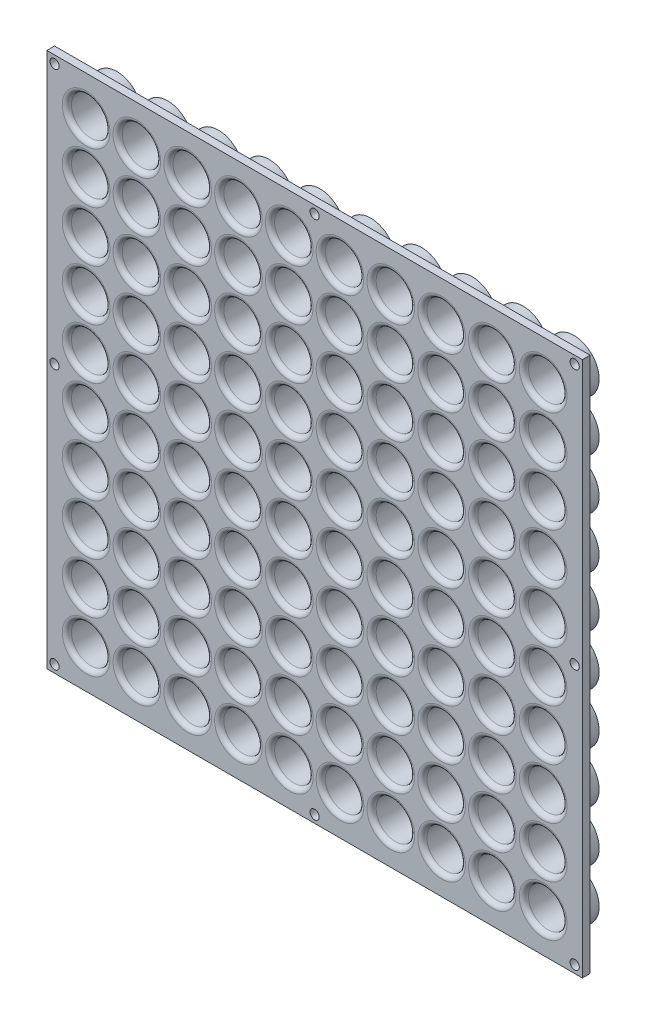
SolidWorks part; units mm, degrees
ref_plane "Ebene vorne" through (0, 0, 0) normal (0, 0, 1) x (1, 0, 0)
ref_plane "Ebene oben" through (0, 0, 0) normal (0, 1, 0) x (1, 0, 0)
ref_plane "Ebene rechts" through (0, 0, 0) normal (1, 0, 0) x (0, 0, -1)
sketch "Sketch1" plane through (0, 0, 0) normal (0, 0, 1) x (1, 0, 0)
  line L1 (0, 0) -> (-250, 0)
  line L2 (0, 0) -> (0, 250)
  line L3 (0, 250) -> (-250, 250)
  line L4 (-250, 0) -> (-250, 250)
  dimension "D1" = 250
  dimension "D2" = 250
extrude "Boss-Extrude1" add sketch "Sketch1" along normal blind 50
sketch "Sketch2" plane through (0, 0, 50) normal (0, 0, 1) x (1, 0, 0)
  line L0 (-125, 250) -> (-125, 0) construction
  line L1 (0, 250) -> (-250, 250) construction
  line L2 (-250, 0) -> (0, 0) construction
  line L5 (0, 0) -> (0, 250) construction
  line L7 (-55, 220) -> (-15, 220)
  line L8 (-55, 220) -> (-55, 120)
  line L9 (-55, 120) -> (-15, 120)
  line L10 (-15, 220) -> (-15, 120)
  line L14 (-55, 95) -> (-15, 95)
  line L15 (-55, 95) -> (-55, 45)
  line L16 (-55, 45) -> (-15, 45)
  line L17 (-15, 95) -> (-15, 45)
  dimension "D1" = 100
  dimension "D2" = 40
  dimension "D3" = 30
  dimension "D4" = 15
  dimension "D5" = 50
  dimension "D6" = 25
extrude "Cut-Extrude1" cut sketch "Sketch2" against normal blind 45
fillet "Fillet1" radius 5 4 edges at (-35, 120, 50) (-15, 170, 50) (-55, 170, 50) (-35, 220, 50)
fillet "Fillet2" radius 5 4 edges at (-35, 45, 50) (-15, 70, 50) (-35, 95, 50) (-55, 70, 50)
sketch "Sketch4" plane through (0, 0, 50) normal (0, 0, 1) x (1, 0, 0)
  line L0 (0, 250) -> (-250, 250) construction
  line L1 (-200, 250) -> (-175, 250)
  line L2 (-200, 250) -> (-200, 232.5)
  line L3 (-200, 232.5) -> (-175, 232.5)
  line L4 (-175, 250) -> (-175, 232.5)
  line L5 (-125, 250) -> (-125, 0) construction
  line L10 (-250, 0) -> (0, 0) construction
  line L11 (-50, 232.5) -> (-75, 232.5)
  line L12 (-75, 250) -> (-75, 232.5)
  line L13 (-50, 250) -> (-75, 250)
  line L14 (-50, 250) -> (-50, 232.5)
  dimension "D1" = 50
  dimension "D2" = 25
  dimension "D3" = 17.5
sketch "Sketch5" plane through (0, 0, 50) normal (0, 0, 1) x (1, 0, 0)
  line L0 (-235, 200) -> (-75, 200) construction
  line L1 (0, 250) -> (-250, 250) construction
  line L2 (-75, 200) -> (-75, 10) construction
  line L3 (-75, 10) -> (-235, 10) construction
  line L4 (-235, 10) -> (-235, 200) construction
  line L5 (-250, 250) -> (-250, 0) construction
  line L6 (-60, 115) -> (-60, 225) construction
  line L7 (-250, 0) -> (0, 0) construction
  line L9 (-235, 200) -> (-215, 200) construction
  line L10 (-235, 200) -> (-235, 180) construction
  line L11 (-235, 180) -> (-215, 180) construction
  line L12 (-215, 200) -> (-215, 180) construction
  line L13 (-235, 200) -> (-215, 180) construction
  line L14 (-235, 180) -> (-215, 200) construction
  circle A0 centre (-225, 190) radius 6.25
  dimension "D5" = 12.5
  dimension "D1" = 15
  dimension "D2" = 50
  dimension "D3" = 15
  dimension "D4" = 10
  dimension "D6" = 20
  dimension "D7" = 20
extrude "Cut-Extrude2" cut sketch "Sketch5" against normal blind 22
fillet "Fillet5" radius 1.5 1 edges at (-218.75, 190, 50)
pattern_linear "LPattern4" count 10 spacing 16.5 along (1, 0, 0) count 10 spacing 16.5 along (0, -1, 0) of "Cut-Extrude2", "Fillet5"
sketch "Sketch7" plane through (0, 0, 0) normal (0, 0, -1) x (-1, 0, 0)
  line L0 (250, 250) -> (250, 0) construction
  line L1 (5, 245) -> (245, 245)
  line L2 (5, 245) -> (5, 225)
  line L3 (5, 5) -> (245, 5)
  line L4 (245, 245) -> (245, 5)
  line L5 (0, 250) -> (250, 250) construction
  line L6 (0, 0) -> (0, 250) construction
  line L7 (250, 0) -> (0, 0) construction
  line L8 (5, 115) -> (5, 100)
  line L9 (5, 225) -> (60, 225)
  line L11 (5, 115) -> (60, 115)
  line L12 (60, 225) -> (60, 115)
  line L13 (5, 40) -> (60, 40)
  line L15 (5, 100) -> (60, 100)
  line L16 (60, 40) -> (60, 100)
  line L17 (5, 40) -> (5, 5)
  line L18 (60, 225) -> (10, 225) construction
  dimension "D1" = 5
  dimension "D2" = 5
  dimension "D3" = 5
  dimension "D4" = 5
extrude "Cut-Extrude4" cut sketch "Sketch7" against normal blind 45
sketch "Sketch8" plane through (0, 0, 50) normal (0, 0, 1) x (1, 0, 0)
  line L0 (0, 250) -> (-250, 250) construction
  line L1 (-175, 250) -> (-75, 250)
  line L2 (-175, 250) -> (-175, 230)
  line L3 (-175, 230) -> (-75, 230)
  line L4 (-75, 250) -> (-75, 230)
  point P6 (-125, 250)
  point P7 (-125, 250)
  dimension "D1" = 100
  dimension "D2" = 20
extrude "Cut-Extrude5" cut sketch "Sketch8" against normal blind 30
fillet "Fillet6" radius 2.5 2 edges at (-125, 230, 45) (-125, 230, 50)
fillet "Fillet7" radius 2 2 edges at (-125, 250, 20) (-125, 245, 20)
sketch "Sketch10" plane through (0, 0, 50) normal (0, 0, 1) x (1, 0, 0)
  line L2 (-35, 40) -> (-35, 0) construction
  line L3 (-10, 40) -> (-60, 40) construction
  line L4 (-250, 0) -> (0, 0) construction
  circle A0 centre (-35, 20) radius 13.5
  dimension "D1" = 27
extrude "Cut-Extrude6" cut sketch "Sketch10" against normal through all
extrude "Cut-Extrude7" cut sketch "Sketch4" against normal blind 10
sketch "Sketch12" plane through (0, 0, 45) normal (0, 0, -1) x (-1, 0, 0)
  line L0 (17.3, 19.25) -> (51.5, 19.25) construction
  line L1 (17.3, 32.5) -> (51.5, 32.5) construction
  line L2 (17.3, 32.5) -> (17.3, 6) construction
  line L3 (17.3, 6) -> (51.5, 6) construction
  line L4 (51.5, 32.5) -> (51.5, 6) construction
  line L5 (35, 40) -> (35, 0) construction
  line L6 (17.3, 20) -> (51.5, 20) construction
  circle A0 centre (46.4, 29.3) radius 2.5
  circle A2 centre (20.1, 29.3) radius 2.5
  circle A3 centre (20.1, 29.3) radius 1.5
  circle A4 centre (46.4, 29.3) radius 1.5
  circle A5 centre (20.1, 9.2) radius 1.5
  circle A6 centre (20.1, 9.2) radius 2.5
  circle A7 centre (46.4, 9.2) radius 1.5
  circle A8 centre (46.4, 9.2) radius 2.5
  dimension "D3" = 5
  dimension "D4" = 2.8
  dimension "D5" = 3.2
  dimension "D6" = 5
  dimension "D7" = 5.1
  dimension "D9" = 3
  dimension "D10" = 3
  dimension "D1" = 34.2
  dimension "D2" = 26.5
  dimension "D8" = 3.2
  dimension "D11" = 16.5
  dimension "D12" = 13.25
  dimension "D13" = 14
fillet "Verrundung1" radius 2.5 2 edges at (-48.5, 20, 45) (-21.5, 20, 50)
sketch "Skizze2" plane through (0, 245, 0) normal (0, -1, 0) x (1, 0, 0)
  line L0 (-175, 18) -> (-175, 40) construction
  line L1 (-175, 40) -> (-200, 40)
  line L2 (-175, 40) -> (-175, 35)
  line L3 (-175, 35) -> (-200, 35)
  line L4 (-200, 40) -> (-200, 35)
  line L5 (-200, 40) -> (-175, 40) construction
  line L6 (-125, 50) -> (-125, 0) construction
  line L7 (-250, 50) -> (0, 50) construction
  line L8 (-250, 0) -> (0, 0) construction
  line L9 (-50, 40) -> (-50, 35)
  line L10 (-75, 35) -> (-50, 35)
  line L11 (-75, 40) -> (-75, 35)
  line L12 (-75, 40) -> (-50, 40)
  dimension "D1" = 25
  dimension "D2" = 5
extrude "Aufsatz-Linear austragen1" add sketch "Skizze2" along normal blind 12.5
sketch "Skizze4" plane through (0, 0, 45) normal (0, 0, -1) x (-1, 0, 0)
  line L0 (75, 232.5) -> (75, 227.5) construction
  line L1 (50, 232.5) -> (75, 232.5)
  line L3 (49, 227.5) -> (75, 227.5)
  line L4 (75, 232.5) -> (75, 227.5)
  line L5 (175, 227.5) -> (175, 232.5) construction
  line L6 (200, 232.5) -> (175, 232.5)
  line L8 (201, 227.5) -> (175, 227.5)
  line L9 (175, 232.5) -> (175, 227.5)
  line L10 (50, 245) -> (5, 245) construction
  line L12 (50, 232.5) -> (50, 245)
  line L13 (50, 245) -> (49, 245)
  line L14 (49, 227.5) -> (49, 245)
  line L15 (245, 245) -> (200, 245) construction
  line L17 (200, 232.5) -> (200, 245)
  line L18 (200, 245) -> (201, 245)
  line L19 (201, 227.5) -> (201, 245)
  dimension "D1" = 5
  dimension "D2" = 5
  dimension "D3" = 1
  dimension "D4" = 1
extrude "Aufsatz-Linear austragen2" add sketch "Skizze4" along normal blind 10
sketch "Skizze8" plane through (0, 0, 0) normal (0, -1, 0) x (1, 0, 0)
  line L0 (-250, 50) -> (0, 50) construction
  line L1 (-250, 0) -> (-245, 0) construction
  line L2 (-250, 0) -> (-250, 50) construction
  line L3 (-250, 50) -> (-245, 50) construction
  line L4 (-245, 0) -> (-245, 50) construction
  line L7 (-245, 7) -> (-248, 7)
  line L9 (-246, 4.7) -> (-248, 4.7)
  line L10 (-248, 7) -> (-248, 4.7)
  line L11 (-246, 4.7) -> (-245, 4.4)
  line L12 (-245, 4.4) -> (-245, 7)
  dimension "D2" = 2.3
  dimension "D1" = 5
  dimension "D3" = 3
  dimension "D4" = 2.6
  dimension "D5" = 2
  dimension "D6" = 7
extrude "Schnitt-Linear austragen3" cut sketch "Skizze8" against normal blind 230 from offset 10 offset against normal yes
sketch "Skizze9" plane through (0, 0, 0) normal (0, -1, 0) x (1, 0, 0)
  line L0 (-250, 0) -> (0, 0) construction
  line L1 (0, 50) -> (-5, 50) construction
  line L2 (0, 50) -> (0, 0) construction
  line L3 (0, 0) -> (-5, 0) construction
  line L4 (-5, 50) -> (-5, 0) construction
  line L6 (-3.734, 5) -> (-4.6, 6.5)
  line L7 (-4.6, 6.5) -> (-6.3321, 6.5)
  line L8 (-6.3321, 6.5) -> (-7.1981, 5)
  line L9 (-7.1981, 5) -> (-6.3321, 3.5)
  line L10 (-6.3321, 3.5) -> (-4.6, 3.5)
  line L11 (-4.6, 3.5) -> (-3.734, 5)
  circle A0 centre (-5.466, 5) radius 1.5 construction
  dimension "D2" = 3
  dimension "D1" = 5
  dimension "D3" = 5
  dimension "D4" = 0.4
extrude "Schnitt-Linear austragen4" cut sketch "Skizze9" against normal blind 25 from offset 10 offset against normal yes
sketch "Skizze10" plane through (0, 250, 0) normal (0, 1, 0) x (1, 0, 0)
  line L1 (-4.6, -3.5) -> (-6.3321, -3.5)
  line L2 (-6.3321, -3.5) -> (-7.1981, -5)
  line L3 (-7.1981, -5) -> (-6.3321, -6.5)
  line L4 (-6.3321, -6.5) -> (-4.6, -6.5)
  line L5 (-4.6, -6.5) -> (-3.734, -5)
  line L6 (-3.734, -5) -> (-4.6, -3.5)
  line L8 (0, -50) -> (0, 0) construction
  line L10 (0, 0) -> (-250, 0) construction
  circle A0 centre (-5.466, -5) radius 1.5 construction
  dimension "D1" = 3
  dimension "D2" = 5
  dimension "D3" = 4.6
extrude "Schnitt-Linear austragen5" cut sketch "Skizze10" against normal blind 10 from offset 10 offset against normal yes
sketch "Skizze11" plane through (0, 0, 50) normal (0, 0, 1) x (1, 0, 0)
  line L0 (-237.75, 202.75) -> (-63.75, 202.75)
  line L1 (-250, 250) -> (0, 250)
  line L2 (-250, 250) -> (-250, 0)
  line L3 (-250, 0) -> (0, 0)
  line L4 (0, 250) -> (0, 0)
  line L5 (-232.75, 197.75) -> (-68.75, 197.75) construction
  line L6 (-232.75, 197.75) -> (-232.75, 33.75) construction
  line L7 (-232.75, 33.75) -> (-68.75, 33.75) construction
  line L8 (-68.75, 197.75) -> (-68.75, 33.75) construction
  line L9 (-63.75, 202.75) -> (-63.75, 28.75)
  line L10 (-237.75, 28.75) -> (-63.75, 28.75)
  line L11 (-237.75, 202.75) -> (-237.75, 28.75)
  circle A0 centre (-225, 190) radius 7.75 construction
  circle A1 centre (-76.5, 190) radius 7.75 construction
  circle A4 centre (-192, 41.5) radius 7.75 construction
  dimension "D1" = 5
extrude "Schnitt-Linear austragen6" cut sketch "Skizze11" against normal through all
sketch "Skizze12" plane through (0, 0, 45) normal (0, 0, -1) x (-1, 0, 0)
  circle A0 centre (76.5, 190) radius 8.2
  circle A1 centre (76.5, 190) radius 6.25
  circle A2 centre (76.5, 190) radius 6.25 construction
  circle A3 centre (93, 190) radius 6.25
  circle A4 centre (93, 190) radius 8.2
  circle A5 centre (109.5, 190) radius 6.25
  circle A6 centre (109.5, 190) radius 8.2
  circle A7 centre (126, 190) radius 6.25
  circle A8 centre (126, 190) radius 8.2
  circle A9 centre (142.5, 190) radius 6.25
  circle A10 centre (142.5, 190) radius 8.2
  circle A11 centre (159, 190) radius 6.25
  circle A12 centre (159, 190) radius 8.2
  circle A13 centre (175.5, 190) radius 6.25
  circle A14 centre (175.5, 190) radius 8.2
  circle A15 centre (192, 190) radius 6.25
  circle A16 centre (192, 190) radius 8.2
  circle A17 centre (208.5, 190) radius 6.25
  circle A18 centre (208.5, 190) radius 8.2
  circle A19 centre (225, 190) radius 6.25
  circle A20 centre (225, 190) radius 8.2
  circle A21 centre (93, 173.5) radius 6.25
  circle A22 centre (93, 173.5) radius 8.2
  circle A23 centre (109.5, 173.5) radius 6.25
  circle A24 centre (109.5, 173.5) radius 8.2
  circle A25 centre (126, 173.5) radius 6.25
  circle A26 centre (126, 173.5) radius 8.2
  circle A27 centre (142.5, 173.5) radius 6.25
  circle A28 centre (142.5, 173.5) radius 8.2
  circle A29 centre (159, 173.5) radius 6.25
  circle A30 centre (159, 173.5) radius 8.2
  circle A31 centre (175.5, 173.5) radius 6.25
  circle A32 centre (175.5, 173.5) radius 8.2
  circle A33 centre (192, 173.5) radius 6.25
  circle A34 centre (192, 173.5) radius 8.2
  circle A35 centre (208.5, 173.5) radius 6.25
  circle A36 centre (208.5, 173.5) radius 8.2
  circle A37 centre (225, 173.5) radius 6.25
  circle A38 centre (225, 173.5) radius 8.2
  circle A39 centre (93, 157) radius 6.25
  circle A40 centre (93, 157) radius 8.2
  circle A41 centre (109.5, 157) radius 6.25
  circle A42 centre (109.5, 157) radius 8.2
  circle A43 centre (126, 157) radius 6.25
  circle A44 centre (126, 157) radius 8.2
  circle A45 centre (142.5, 157) radius 6.25
  circle A46 centre (142.5, 157) radius 8.2
  circle A47 centre (159, 157) radius 6.25
  circle A48 centre (159, 157) radius 8.2
  circle A49 centre (175.5, 157) radius 6.25
  circle A50 centre (175.5, 157) radius 8.2
  circle A51 centre (192, 157) radius 6.25
  circle A52 centre (192, 157) radius 8.2
  circle A53 centre (208.5, 157) radius 6.25
  circle A54 centre (208.5, 157) radius 8.2
  circle A55 centre (225, 157) radius 6.25
  circle A56 centre (225, 157) radius 8.2
  circle A57 centre (93, 140.5) radius 6.25
  circle A58 centre (93, 140.5) radius 8.2
  circle A59 centre (109.5, 140.5) radius 6.25
  circle A60 centre (109.5, 140.5) radius 8.2
  circle A61 centre (126, 140.5) radius 6.25
  circle A62 centre (126, 140.5) radius 8.2
  circle A63 centre (142.5, 140.5) radius 6.25
  circle A64 centre (142.5, 140.5) radius 8.2
  circle A65 centre (159, 140.5) radius 6.25
  circle A66 centre (159, 140.5) radius 8.2
  circle A67 centre (175.5, 140.5) radius 6.25
  circle A68 centre (175.5, 140.5) radius 8.2
  circle A69 centre (192, 140.5) radius 6.25
  circle A70 centre (192, 140.5) radius 8.2
  circle A71 centre (208.5, 140.5) radius 6.25
  circle A72 centre (208.5, 140.5) radius 8.2
  circle A73 centre (225, 140.5) radius 6.25
  circle A74 centre (225, 140.5) radius 8.2
  circle A75 centre (93, 124) radius 6.25
  circle A76 centre (93, 124) radius 8.2
  circle A77 centre (109.5, 124) radius 6.25
  circle A78 centre (109.5, 124) radius 8.2
  circle A79 centre (126, 124) radius 6.25
  circle A80 centre (126, 124) radius 8.2
  circle A81 centre (142.5, 124) radius 6.25
  circle A82 centre (142.5, 124) radius 8.2
  circle A83 centre (159, 124) radius 6.25
  circle A84 centre (159, 124) radius 8.2
  circle A85 centre (175.5, 124) radius 6.25
  circle A86 centre (175.5, 124) radius 8.2
  circle A87 centre (192, 124) radius 6.25
  circle A88 centre (192, 124) radius 8.2
  circle A89 centre (208.5, 124) radius 6.25
  circle A90 centre (208.5, 124) radius 8.2
  circle A91 centre (225, 124) radius 6.25
  circle A92 centre (225, 124) radius 8.2
  circle A93 centre (93, 107.5) radius 6.25
  circle A94 centre (93, 107.5) radius 8.2
  circle A95 centre (109.5, 107.5) radius 6.25
  circle A96 centre (109.5, 107.5) radius 8.2
  circle A97 centre (126, 107.5) radius 6.25
  circle A98 centre (126, 107.5) radius 8.2
  circle A99 centre (142.5, 107.5) radius 6.25
  circle A100 centre (142.5, 107.5) radius 8.2
  circle A101 centre (159, 107.5) radius 6.25
  circle A102 centre (159, 107.5) radius 8.2
  circle A103 centre (175.5, 107.5) radius 6.25
  circle A104 centre (175.5, 107.5) radius 8.2
  circle A105 centre (192, 107.5) radius 6.25
  circle A106 centre (192, 107.5) radius 8.2
  circle A107 centre (208.5, 107.5) radius 6.25
  circle A108 centre (208.5, 107.5) radius 8.2
  circle A109 centre (225, 107.5) radius 6.25
  circle A110 centre (225, 107.5) radius 8.2
  circle A111 centre (93, 91) radius 6.25
  circle A112 centre (93, 91) radius 8.2
  circle A113 centre (109.5, 91) radius 6.25
  circle A114 centre (109.5, 91) radius 8.2
  circle A115 centre (126, 91) radius 6.25
  circle A116 centre (126, 91) radius 8.2
  circle A117 centre (142.5, 91) radius 6.25
  circle A118 centre (142.5, 91) radius 8.2
  circle A119 centre (159, 91) radius 6.25
  circle A120 centre (159, 91) radius 8.2
  circle A121 centre (175.5, 91) radius 6.25
  circle A122 centre (175.5, 91) radius 8.2
  circle A123 centre (192, 91) radius 6.25
  circle A124 centre (192, 91) radius 8.2
  circle A125 centre (208.5, 91) radius 6.25
  circle A126 centre (208.5, 91) radius 8.2
  circle A127 centre (225, 91) radius 6.25
  circle A128 centre (225, 91) radius 8.2
  circle A129 centre (93, 74.5) radius 6.25
  circle A130 centre (93, 74.5) radius 8.2
  circle A131 centre (109.5, 74.5) radius 6.25
  circle A132 centre (109.5, 74.5) radius 8.2
  circle A133 centre (126, 74.5) radius 6.25
  circle A134 centre (126, 74.5) radius 8.2
  circle A135 centre (142.5, 74.5) radius 6.25
  circle A136 centre (142.5, 74.5) radius 8.2
  circle A137 centre (159, 74.5) radius 6.25
  circle A138 centre (159, 74.5) radius 8.2
  circle A139 centre (175.5, 74.5) radius 6.25
  circle A140 centre (175.5, 74.5) radius 8.2
  circle A141 centre (192, 74.5) radius 6.25
  circle A142 centre (192, 74.5) radius 8.2
  circle A143 centre (208.5, 74.5) radius 6.25
  circle A144 centre (208.5, 74.5) radius 8.2
  circle A145 centre (225, 74.5) radius 6.25
  circle A146 centre (225, 74.5) radius 8.2
  circle A147 centre (93, 58) radius 6.25
  circle A148 centre (93, 58) radius 8.2
  circle A149 centre (109.5, 58) radius 6.25
  circle A150 centre (109.5, 58) radius 8.2
  circle A151 centre (126, 58) radius 6.25
  circle A152 centre (126, 58) radius 8.2
  circle A153 centre (142.5, 58) radius 6.25
  circle A154 centre (142.5, 58) radius 8.2
  circle A155 centre (159, 58) radius 6.25
  circle A156 centre (159, 58) radius 8.2
  circle A157 centre (175.5, 58) radius 6.25
  circle A158 centre (175.5, 58) radius 8.2
  circle A159 centre (192, 58) radius 6.25
  circle A160 centre (192, 58) radius 8.2
  circle A161 centre (208.5, 58) radius 6.25
  circle A162 centre (208.5, 58) radius 8.2
  circle A163 centre (225, 58) radius 6.25
  circle A164 centre (225, 58) radius 8.2
  circle A165 centre (93, 41.5) radius 6.25
  circle A166 centre (93, 41.5) radius 8.2
  circle A167 centre (109.5, 41.5) radius 6.25
  circle A168 centre (109.5, 41.5) radius 8.2
  circle A169 centre (126, 41.5) radius 6.25
  circle A170 centre (126, 41.5) radius 8.2
  circle A171 centre (142.5, 41.5) radius 6.25
  circle A172 centre (142.5, 41.5) radius 8.2
  circle A173 centre (159, 41.5) radius 6.25
  circle A174 centre (159, 41.5) radius 8.2
  circle A175 centre (175.5, 41.5) radius 6.25
  circle A176 centre (175.5, 41.5) radius 8.2
  circle A177 centre (192, 41.5) radius 6.25
  circle A178 centre (192, 41.5) radius 8.2
  circle A179 centre (208.5, 41.5) radius 6.25
  circle A180 centre (208.5, 41.5) radius 8.2
  circle A181 centre (225, 41.5) radius 6.25
  circle A182 centre (225, 41.5) radius 8.2
  circle A183 centre (76.5, 173.5) radius 6.25
  circle A184 centre (76.5, 173.5) radius 8.2
  circle A185 centre (76.5, 157) radius 6.25
  circle A186 centre (76.5, 157) radius 8.2
  circle A187 centre (76.5, 140.5) radius 6.25
  circle A188 centre (76.5, 140.5) radius 8.2
  circle A189 centre (76.5, 124) radius 6.25
  circle A190 centre (76.5, 124) radius 8.2
  circle A191 centre (76.5, 107.5) radius 6.25
  circle A192 centre (76.5, 107.5) radius 8.2
  circle A193 centre (76.5, 91) radius 6.25
  circle A194 centre (76.5, 91) radius 8.2
  circle A195 centre (76.5, 74.5) radius 6.25
  circle A196 centre (76.5, 74.5) radius 8.2
  circle A197 centre (76.5, 58) radius 6.25
  circle A198 centre (76.5, 58) radius 8.2
  circle A199 centre (76.5, 41.5) radius 6.25
  circle A200 centre (76.5, 41.5) radius 8.2
  circle A201 centre (225, 41.5) radius 6.25 construction
  circle A202 centre (225, 190) radius 6.25 construction
  dimension "D1" = 16.4
  dimension "D2" = 10
  dimension "D3" = 10
extrude "Aufsatz-Linear austragen3" add sketch "Skizze12" along normal blind 5
sketch "Skizze14" plane through (0, 0, 50) normal (0, 0, 1) x (1, 0, 0)
  line L0 (-68.75, 115.75) -> (-63.75, 115.75) construction
  line L1 (-68.75, 197.75) -> (-68.75, 33.75) construction
  line L2 (-63.75, 202.75) -> (-63.75, 28.75) construction
  line L3 (-150.75, 197.75) -> (-150.75, 202.75) construction
  line L4 (-232.75, 197.75) -> (-68.75, 197.75) construction
  line L5 (-237.75, 202.75) -> (-63.75, 202.75) construction
  line L6 (-232.75, 115.75) -> (-237.75, 115.75) construction
  line L8 (-232.75, 197.75) -> (-232.75, 33.75) construction
  line L9 (-237.75, 202.75) -> (-237.75, 28.75) construction
  line L10 (-150.75, 33.75) -> (-150.75, 28.75) construction
  line L11 (-232.75, 33.75) -> (-68.75, 33.75) construction
  line L12 (-237.75, 28.75) -> (-63.75, 28.75) construction
  circle A0 centre (-235.25, 200.25) radius 1.5
  circle A1 centre (-150.75, 200.25) radius 1.5
  circle A2 centre (-66.25, 200.25) radius 1.5
  circle A3 centre (-235.25, 115.75) radius 1.5
  circle A4 centre (-66.25, 115.75) radius 1.5
  circle A5 centre (-66.25, 31.25) radius 1.5
  circle A6 centre (-150.75, 31.25) radius 1.5
  circle A7 centre (-235.25, 31.25) radius 1.5
  point P31 (-235.25, 115.75)
  point P32 (-66.25, 115.75)
  dimension "D1" = 3
  dimension "D2" = 3
  dimension "D3" = 3
  dimension "D4" = 3
  dimension "D5" = 3
extrude "Schnitt-Linear austragen7" cut sketch "Skizze14" against normal blind 5
sketch "Skizze15" plane through (0, 0, 45) normal (0, 0, -1) x (-1, 0, 0)
  line L1 (63.75, 202.75) -> (237.75, 202.75)
  line L2 (63.75, 202.75) -> (63.75, 28.75)
  line L3 (63.75, 28.75) -> (237.75, 28.75)
  line L4 (237.75, 202.75) -> (237.75, 28.75)
  line L5 (68.3, 198.2) -> (233.2, 198.2)
  line L6 (68.3, 198.2) -> (68.3, 33.3)
  line L7 (68.3, 33.3) -> (233.2, 33.3)
  line L8 (233.2, 198.2) -> (233.2, 33.3)
  circle A0 centre (76.5, 190) radius 8.2 construction
  circle A1 centre (76.5, 190) radius 8.2 construction
  circle A2 centre (225, 190) radius 8.2 construction
  circle A3 centre (225, 41.5) radius 8.2 construction
extrude "Schnitt-Linear austragen8" cut sketch "Skizze15" against normal blind 2.5
fillet "Verrundung3" radius 2.5 4 edges at (-68.3, 33.3, 46.25) (-233.2, 33.3, 46.25) (-233.2, 198.2, 46.25) (-68.3, 198.2, 46.25)
